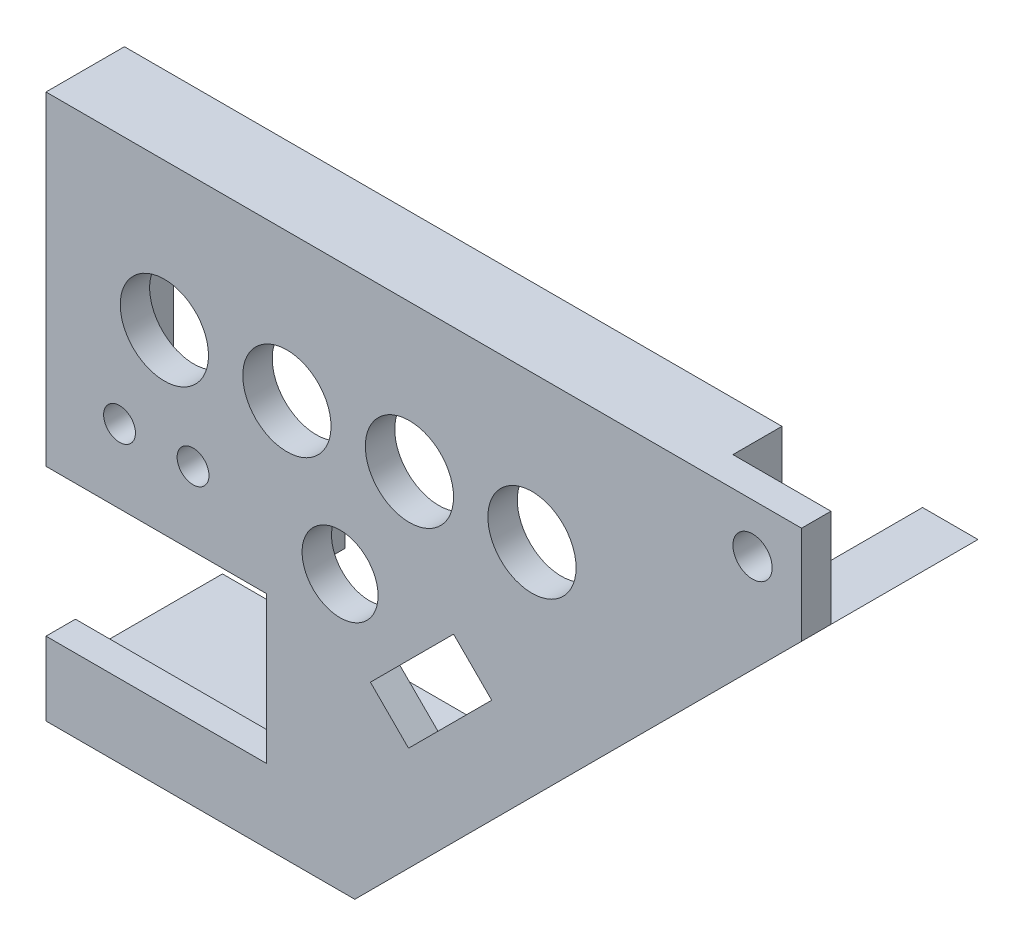
SolidWorks part; units mm, degrees
ref_plane "Plan de face" through (0, 0, 0) normal (0, 0, 1) x (1, 0, 0)
ref_plane "Plan de dessus" through (0, 0, 0) normal (0, 1, 0) x (1, 0, 0)
ref_plane "Plan de droite" through (0, 0, 0) normal (1, 0, 0) x (0, 0, -1)
sketch "Esquisse1" plane through (0, 0, 0) normal (0, 0, 1) x (1, 0, 0)
  line L0 (0, 0) -> (63, 0)
  line L1 (63, 0) -> (154.15, 91.15)
  line L2 (154.15, 91.15) -> (154.15, 111.15)
  line L3 (0, 111.15) -> (0, 0)
  line L4 (154.15, 111.15) -> (0, 111.15)
  dimension "D1" = 135
  dimension "D2" = 154.15
  dimension "D3" = 63
  dimension "D4" = 20
  dimension "D5" = 128.9056
extrude "Boss.-Extru.1" add sketch "Esquisse1" along normal blind 6
sketch "Esquisse2" plane through (0, 0, 6) normal (0, 0, 1) x (1, 0, 0)
  line L0 (0, 0) -> (63, 0) construction
  line L2 (154.15, 91.15) -> (154.15, 111.15) construction
  line L3 (66.1881, 39.9576) -> (73.9662, 32.1794)
  line L4 (73.9662, 32.1794) -> (90.9368, 49.15)
  line L5 (90.9368, 49.15) -> (83.1586, 56.9282)
  line L6 (83.1586, 56.9282) -> (66.1881, 39.9576)
  line L7 (63, 0) -> (154.15, 91.15) construction
  line L9 (154.15, 111.15) -> (0, 111.15) construction
  line L10 (0, 111.15) -> (0, 0) construction
  line L11 (0, 111.15) -> (0, 0) construction
  circle A0 centre (49.15, 81.15) radius 9
  circle A1 centre (74.15, 81.15) radius 9
  circle A2 centre (99.15, 81.15) radius 9
  circle A3 centre (24.15, 81.15) radius 9
  circle A4 centre (60, 56) radius 7.75
  circle A5 centre (30, 60) radius 3.25
  circle A6 centre (15, 60) radius 3.25
  point P14 (154.15, 101.15)
  dimension "D1" = 18
  dimension "D4" = 25
  dimension "D11" = 15.5
  dimension "D5" = 6.5
  dimension "D2" = 25
  dimension "D3" = 25
  dimension "D6" = 55
  dimension "D7" = 11
  dimension "D8" = 24
  dimension "D9" = 15
  dimension "D10" = 62
  dimension "D12" = 56
  dimension "D13" = 60
  dimension "D14" = 30
  dimension "D15" = 30
  dimension "D16" = 60
  dimension "D17" = 15
extrude "Enlèv. mat.-Extru.1" cut sketch "Esquisse2" against normal through all
sketch "Esquisse3" plane through (0, 0, 6) normal (0, 0, 1) x (1, 0, 0)
  line L0 (0, 111.15) -> (0, 0) construction
  line L1 (0, 45) -> (45, 45)
  line L2 (0, 45) -> (0, 15)
  line L3 (0, 15) -> (45, 15)
  line L4 (45, 45) -> (45, 15)
  line L5 (0, 0) -> (63, 0) construction
  dimension "D1" = 45
  dimension "D2" = 45
  dimension "D3" = 30
extrude "Enlèv. mat.-Extru.2" cut sketch "Esquisse3" against normal through all
sketch "Esquisse6" plane through (0, 0, 0) normal (0, 0, -1) x (-1, 0, 0)
  line L0 (-154.15, 91.15) -> (-142.8363, 91.15)
  line L1 (-142.8363, 91.15) -> (-59.6863, 8)
  line L2 (-59.6863, 8) -> (0, 8)
  line L3 (0, 15) -> (0, 0) construction
  line L4 (0, 8) -> (0, 0)
  line L5 (0, 0) -> (-63, 0)
  line L6 (-63, 0) -> (-154.15, 91.15) construction
  line L7 (0, 0) -> (-63, 0) construction
  line L8 (-63, 0) -> (-154.15, 91.15)
  dimension "D1" = 8
  dimension "D2" = 8
extrude "Boss.-Extru.2" add sketch "Esquisse6" along normal blind 30
sketch "Esquisse7" plane through (0, 0, 0) normal (0, 0, -1) x (-1, 0, 0)
  line L0 (-10, 55) -> (-45, 55)
  line L2 (-10, 55) -> (-10, 105.15)
  line L3 (-10, 105.15) -> (-128.15, 105.15)
  line L4 (-134.15, 111.15) -> (0, 111.15)
  line L5 (-154.15, 111.15) -> (0, 111.15) construction
  line L6 (0, 111.15) -> (0, 45)
  line L7 (-128.15, 76.4637) -> (-142.8363, 91.15)
  line L8 (-59.6863, 8) -> (-142.8363, 91.15) construction
  line L9 (-59.6863, 8) -> (-142.8363, 91.15) construction
  line L10 (-142.8363, 91.15) -> (-134.15, 91.15)
  line L11 (-128.15, 105.15) -> (-128.15, 76.4637)
  line L13 (-134.15, 91.15) -> (-134.15, 111.15)
  line L14 (-45, 55) -> (-45, 45)
  line L15 (-45, 45) -> (0, 45)
  line L16 (-45, 15) -> (-45, 45) construction
  dimension "D1" = 6
  dimension "D2" = 10
  dimension "D3" = 20
  dimension "D4" = 6
  dimension "D5" = 10
extrude "Boss.-Extru.3" add sketch "Esquisse7" along normal blind 10
sketch "Esquisse8" plane through (0, 0, 6) normal (0, 0, 1) x (1, 0, 0)
  line L0 (154.15, 91.15) -> (154.15, 111.15) construction
  line L1 (154.15, 111.15) -> (0, 111.15) construction
  circle A0 centre (144.15, 101.15) radius 4
  dimension "D3" = 8
  dimension "D1" = 10
  dimension "D2" = 10
extrude "Enlèv. mat.-Extru.3" cut sketch "Esquisse8" against normal through all
sketch "Esquisse9" plane through (0, 0, 0) normal (-1, 0, 0) x (0, 0, 1)
  line L0 (-10, 45) -> (-10, 111.15) construction
  line L1 (6, 111.15) -> (-10, 111.15) construction
  circle A0 centre (-5, 101.15) radius 1.35
  dimension "D1" = 2.7
  dimension "D2" = 5
  dimension "D3" = 10
extrude "Enlèv. mat.-Extru.4" cut sketch "Esquisse9" against normal up to next
pattern_linear "Répétition linéaire1" count 3 spacing 20 along (0, -1, 0) of "Enlèv. mat.-Extru.4"
sketch "Esquisse10" plane through (0, 0, 0) normal (-1, 0, 0) x (0, 0, 1)
  line L0 (6, 111.15) -> (-10, 111.15) construction
  line L1 (6, 111.15) -> (6, 45) construction
  line L2 (6, 0) -> (-30, 0) construction
  line L3 (6, 15) -> (6, 0) construction
  line L4 (0, 15) -> (0, 8) construction
  circle A0 centre (0, 91.15) radius 3
  circle A1 centre (0, 71.15) radius 3
  circle A2 centre (0, 51.15) radius 3
  circle A3 centre (-14, 4) radius 3
  circle A4 centre (0, 4) radius 3
  dimension "D2" = 6
  dimension "D1" = 20
  dimension "D3" = 20
  dimension "D4" = 20
  dimension "D5" = 6
  dimension "D6" = 4
  dimension "D8" = 20
extrude "Enlèv. mat.-Extru.5" cut sketch "Esquisse10" against normal up to surface (10 mm away) up to face at (10, 79.8, -5)
sketch "Esquisse11" plane through (0, 0, 0) normal (0, -1, 0) x (1, 0, 0)
  line L0 (63, 6) -> (63, -30) construction
  line L1 (0, -30) -> (63, -30)
  line L2 (0, -30) -> (0, -20)
  line L3 (0, -20) -> (63, -20)
  line L4 (63, -30) -> (63, -20)
  dimension "D1" = 10
extrude "Enlèv. mat.-Extru.6" cut sketch "Esquisse11" against normal blind 5
sketch "Esquisse12" plane through (31.5, -31.5, 0) normal (0.7071, -0.7071, 0) x (0, 0, -1)
  line L0 (30, 173.4533) -> (30, 44.5477) construction
  line L1 (20, 65.5005) -> (30, 65.5005)
  line L2 (20, 65.5005) -> (20, 152.5005)
  line L3 (20, 152.5005) -> (30, 152.5005)
  line L4 (30, 65.5005) -> (30, 152.5005)
  point P7 (30, 109.0005)
  dimension "D1" = 10
  dimension "D2" = 87
extrude "Enlèv. mat.-Extru.7" cut sketch "Esquisse12" against normal blind 5
